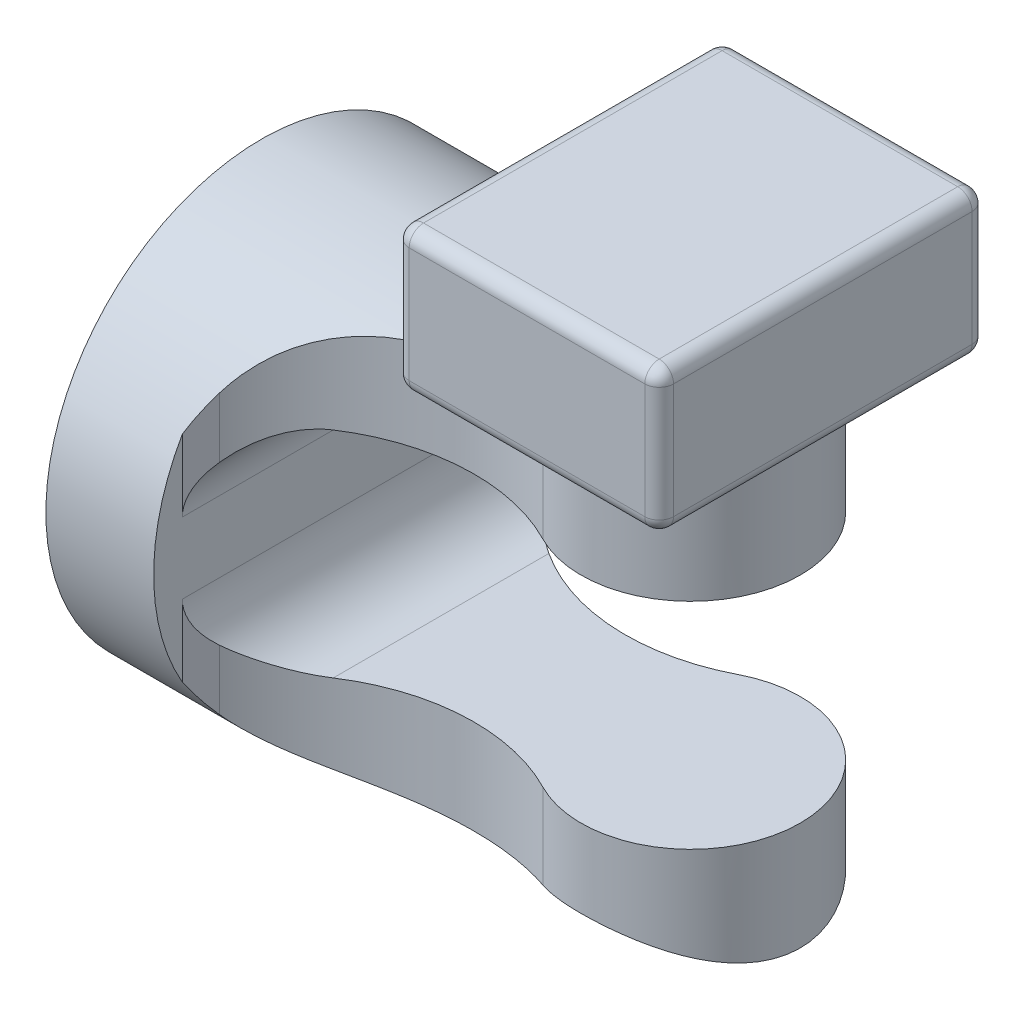
SolidWorks part; units mm, degrees
material "6061 Alloy"
ref_plane "Front Plane" through (0, 0, 0) normal (0, 0, 1) x (1, 0, 0)
ref_plane "Top Plane" through (0, 0, 0) normal (0, 1, 0) x (1, 0, 0)
ref_plane "Right Plane" through (0, 0, 0) normal (1, 0, 0) x (0, 0, -1)
sketch "Sketch1" plane through (0, 0, 0) normal (1, 0, 0) x (0, 0, -1)
  circle A0 centre (0, 0) radius 150
  dimension "D1" = 300
extrude "Boss-Extrude1" add sketch "Sketch1" along normal blind 75
sketch "Sketch2" plane through (0, 0, 0) normal (0, 0, 1) x (1, 0, 0)
  line L0 (75, 150) -> (75, -150)
  line L1 (75, -150) -> (375, -150)
  line L2 (375, -150) -> (375, -74.7251)
  line L3 (375, -74.7251) -> (75, -74.7251)
  dimension "D1" = 300
extrude "Boss-Extrude2" add sketch "Sketch2" along normal up to surface and the other way up to surface contours L2 L3 L0 L1 region at (225, -112.3626, 0) up to face at (75, 0, -150) other way up to face at (75, 0, -150)
sketch "Sketch3" plane through (0, -74.7251, 0) normal (0, 1, 0) x (1, 0, 0)
  line L0 (75, 130.0621) -> (85.2927, 114.4995)
  line L1 (85.2927, -114.4995) -> (75, -130.0621)
  line L2 (263.7532, 67.8646) -> (263.7532, -67.8646)
  line L3 (298.6766, 0) -> (263.7532, 0)
  line L4 (263.7532, 0) -> (0, 0)
  line L5 (375, -130.0621) -> (375, 130.0621) construction
  line L6 (75, 130.0621) -> (375, 130.0621)
  line L7 (375, 130.0621) -> (375, 0)
  line L8 (375, 0) -> (375, -130.0621)
  line L9 (375, -130.0621) -> (75, -130.0621)
  arc A0 (85.2927, 114.4995) -> (263.7532, 67.8646) centre (200.5331, 190.7165) ccw
  arc A1 (263.7532, 67.8646) -> (237.5211, -45.6646) centre (298.6766, 0) cw
  arc A2 (237.5211, -45.6646) -> (263.7532, -67.8646) centre (298.6766, 0) cw
  arc A3 (263.7532, -67.8646) -> (85.2927, -114.4995) centre (200.5331, -190.7165) ccw
  line M7 (75, -130.0621) -> (375, -130.0621)
  line M8 (375, -130.0621) -> (375, 130.0621)
  line M9 (375, 130.0621) -> (75, 130.0621)
extrude "Cut-Extrude1" cut sketch "Sketch3" against normal through all contours A0 A1 L0 M8 M9 | A2 A3 L1 A1 M7 M8 region at (238.5908, -74.7251, -95.9663) region at (238.5908, -74.7251, 95.9663)
mirror "Mirror1" about plane through (0, 0, 0) normal (0, 1, 0) of "Cut-Extrude1", "Boss-Extrude2"
sketch "Sketch4" plane through (0, 74.7251, 0) normal (0, -1, 0) x (1, 0, 0)
  circle A0 centre (298.6766, 0) radius 50
  dimension "D1" = 100
extrude "Boss-Extrude3" add sketch "Sketch4" against normal blind 85
sketch "Sketch5" plane through (0, 159.7251, 0) normal (0, 1, 0) x (1, 0, 0)
  line L1 (206.6904, 113.8736) -> (390.6629, 113.8736)
  line L2 (206.6904, 113.8736) -> (206.6904, -113.8736)
  line L3 (206.6904, -113.8736) -> (390.6629, -113.8736)
  line L4 (390.6629, 113.8736) -> (390.6629, -113.8736)
  line L5 (206.6904, 113.8736) -> (390.6629, -113.8736) construction
  line L6 (206.6904, -113.8736) -> (390.6629, 113.8736) construction
  circle A1 centre (298.6766, 0) radius 50
  circle A2 centre (298.6766, 0) radius 50 construction
  dimension "D1" = 0
extrude "Boss-Extrude4" add sketch "Sketch5" along normal blind 100
fillet "Fillet1" radius 10 12 edges at (206.6904, 159.7251, 0) (206.6904, 209.7251, 113.8736) (298.6766, 159.7251, 113.8736) (390.6629, 209.7251, 113.8736) (390.6629, 159.7251, 0) (298.6766, 259.7251, 113.8736) (206.6904, 259.7251, 0) (390.6629, 259.7251, 0) (390.6629, 209.7251, -113.8736) (298.6766, 259.7251, -113.8736) (206.6904, 209.7251, -113.8736) (298.6766, 159.7251, -113.8736)
fillet "Fillet2" radius 50 2 edges at (75, 74.7251, 0) (75, -74.7251, 0)
